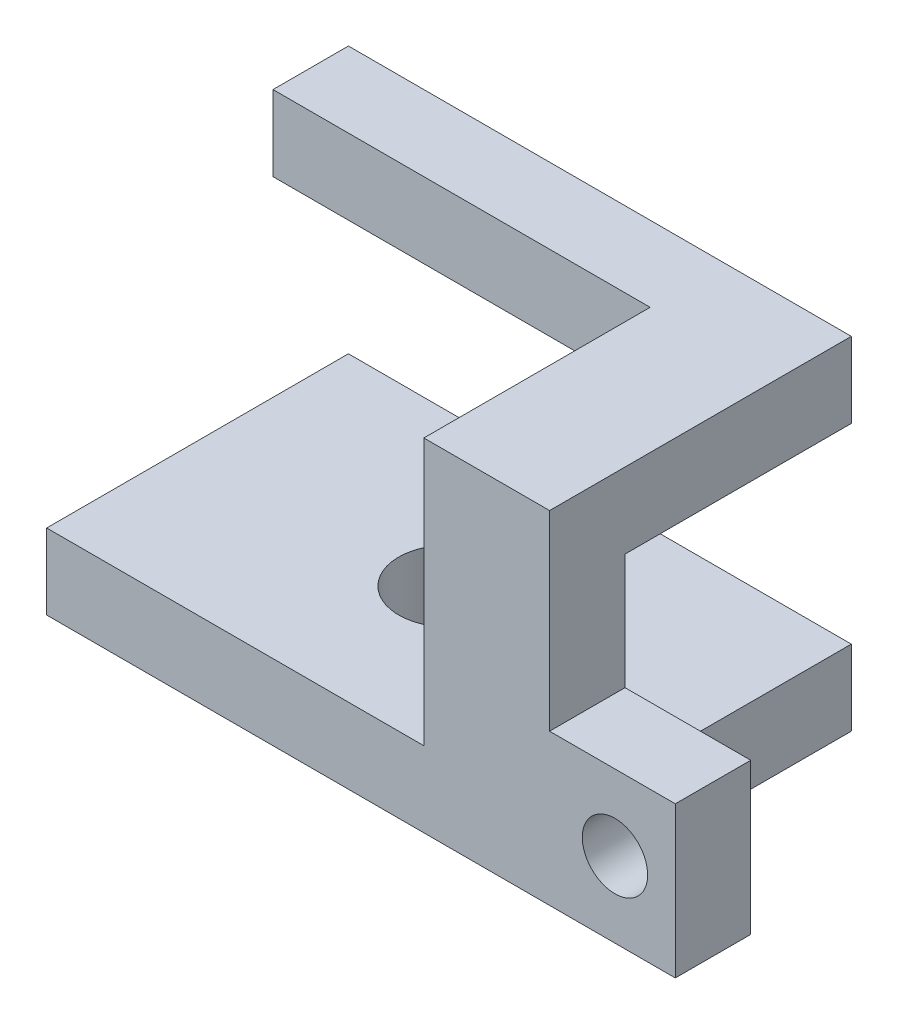
SolidWorks part; units mm, degrees
ref_plane "Front Plane" through (0, 0, 0) normal (0, 0, 1) x (1, 0, 0)
ref_plane "Top Plane" through (0, 0, 0) normal (0, 1, 0) x (1, 0, 0)
ref_plane "Right Plane" through (0, 0, 0) normal (1, 0, 0) x (0, 0, -1)
sketch "Sketch1" plane through (0, 0, 0) normal (0, 1, 0) x (1, 0, 0)
  line L1 (-50, -30) -> (50, -30)
  line L2 (-50, -30) -> (-50, 30)
  line L3 (-50, 30) -> (50, 30)
  line L5 (-50, -30) -> (50, 30) construction
  line L6 (-50, 30) -> (50, -30) construction
  line L7 (50, 30) -> (75, 30)
  line L9 (50, -30) -> (75, -30)
  line L10 (75, 30) -> (75, -30)
  circle A0 centre (0, 0) radius 10
  point P0 (0, 0)
  dimension "D3" = 20
  dimension "D1" = 60
  dimension "D2" = 100
  dimension "D4" = 25
extrude "Boss-Extrude1" add sketch "Sketch1" along normal blind 68
sketch "Sketch3" plane through (75, 0, 0) normal (1, 0, 0) x (0, 0, -1)
  line L0 (30, 68) -> (30, 0) construction
  line L1 (30, 53) -> (-15, 53)
  line L2 (30, 53) -> (30, 15)
  line L3 (30, 15) -> (-15, 15)
  line L4 (-15, 53) -> (-15, 15)
  line L5 (30, 34) -> (-0.7634, 34) construction
  line L6 (-30, 68) -> (30, 68) construction
  line L7 (-30, 68) -> (-30, 0) construction
  line L8 (-30, 0) -> (30, 0) construction
  dimension "D1" = 15
  dimension "D2" = 15
  dimension "D3" = 15
extrude "Cut-Extrude1" cut sketch "Sketch3" against normal through all
sketch "Sketch4" plane through (0, 68, 0) normal (0, 1, 0) x (1, 0, 0)
  line L0 (-50, 30) -> (-50, -30) construction
  line L1 (-50, 15) -> (25, 15)
  line L2 (-50, 15) -> (-50, -30)
  line L3 (-50, -30) -> (25, -30)
  line L4 (25, 15) -> (25, -30)
  line L5 (-50, -30) -> (75, -30) construction
  line L6 (75, 30) -> (-50, 30) construction
  line L7 (75, -30) -> (75, 30) construction
  line L9 (50, 30) -> (75, 30)
  line L10 (50, 30) -> (50, -15)
  line L11 (50, -15) -> (75, -15)
  line L12 (75, 30) -> (75, -15)
  line M5 (75, 30) -> (-50, 30)
  line M8 (75, -30) -> (75, 30)
  dimension "D1" = 15
  dimension "D2" = 50
  dimension "D3" = 15
  dimension "D4" = 25
extrude "Cut-Extrude2" cut sketch "Sketch4" against normal up to surface (53 mm away) up to face at (0, 15, -10)
extrude "Cut-Extrude3" cut sketch "Sketch4<2>" against normal through all contours L10 L11 M8 M5 region at (62.5, 68, -7.5)
sketch "Sketch4<2>" plane through (0, 68, 0) normal (0, 1, 0) x (1, 0, 0) same geometry as "Sketch4"
sketch "Sketch5" plane through (0, 0, 15) normal (0, 0, -1) x (-1, 0, 0)
  line L0 (-50, 0) -> (-75, 0) construction
  line L1 (-75, 68) -> (-50, 68)
  line L2 (-75, 68) -> (-75, 30)
  line L3 (-75, 30) -> (-50, 30)
  line L4 (-50, 68) -> (-50, 30)
  line L6 (-75, 68) -> (-75, 0) construction
  line L7 (-75, 30) -> (-75, 0) construction
  line L8 (-75, 0) -> (-75, 15) construction
  line L9 (-75, 15) -> (-50, 15) construction
  circle A0 centre (-63, 15) radius 6.5
  point P11 (0, 0)
  dimension "D2" = 13
  dimension "D3" = 12
  dimension "D1" = 30
extrude "Cut-Extrude4" cut sketch "Sketch5" against normal through all
